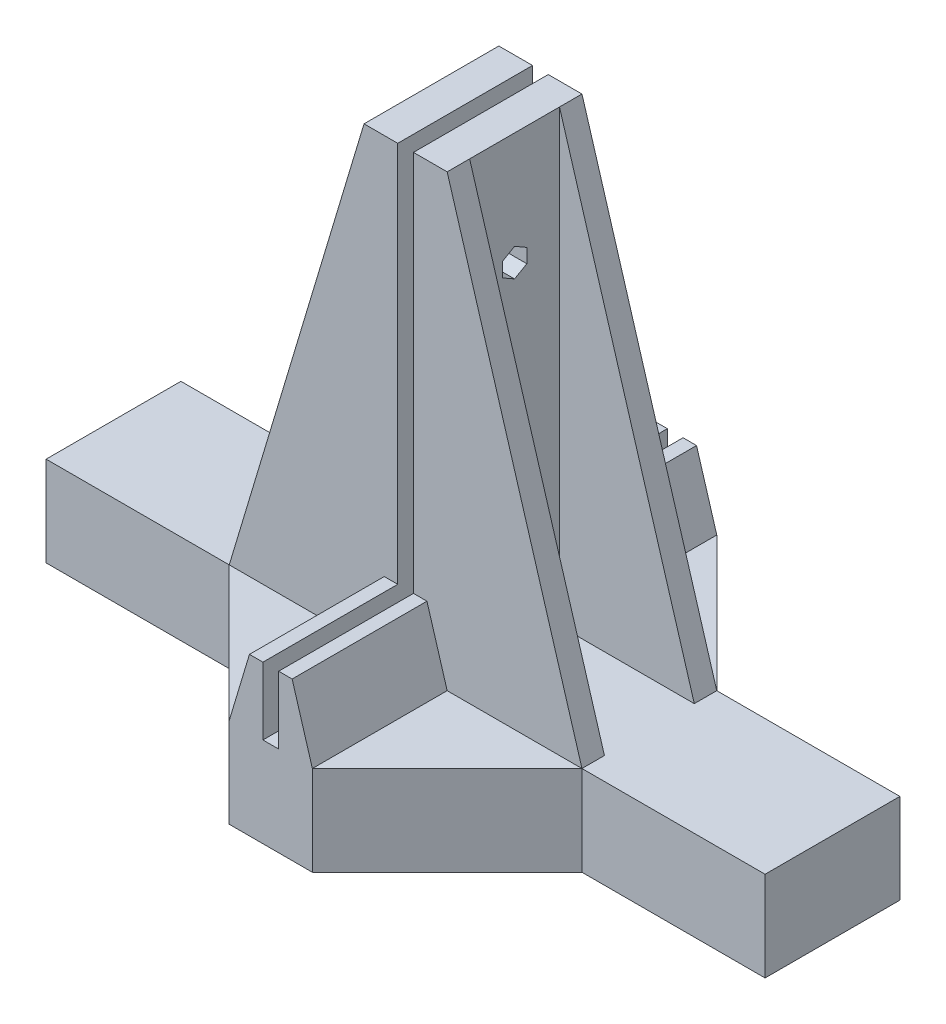
SolidWorks part; units mm, degrees
ref_plane "Front Plane" through (0, 0, 0) normal (0, 0, 1) x (1, 0, 0)
ref_plane "Top Plane" through (0, 0, 0) normal (0, 1, 0) x (1, 0, 0)
ref_plane "Right Plane" through (0, 0, 0) normal (1, 0, 0) x (0, 0, -1)
sketch "Sketch1" plane through (0, 0, 0) normal (0, 0, 1) x (1, 0, 0)
  line L0 (0, 0) -> (80, 0)
  line L1 (55, 0) -> (-55, 0) construction
  line L2 (80, 0) -> (80, 20)
  line L3 (80, 20) -> (9.25, 20)
  line L4 (9.25, 20) -> (9.25, 120)
  line L5 (9.25, 120) -> (1.75, 120)
  line L6 (1.75, 120) -> (1.75, 20)
  line L7 (1.75, 20) -> (-1.75, 20)
  line L8 (-1.75, 20) -> (-1.75, 120)
  line L9 (-1.75, 120) -> (-9.25, 120)
  line L10 (-9.25, 120) -> (-9.25, 20)
  line L11 (-9.25, 20) -> (-80, 20)
  line L12 (-80, 20) -> (-80, 0)
  line L13 (-80, 0) -> (0, 0)
  point P15 (0, 20)
  point P17 (1.6, 20)
  dimension "D1" = 80
  dimension "D2" = 20
  dimension "D4" = 100
  dimension "D5" = 7.5
  dimension "D6" = 3.5
  dimension "D7" = 160
  dimension "D8" = 7.5
extrude "Boss-Extrude3" add sketch "Sketch1" along normal blind 30
sketch "Sketch3" plane through (9.25, 0, 0) normal (1, 0, 0) x (0, 0, -1)
  line L0 (-30, 120) -> (0, 120) construction
  line L3 (-30, 20) -> (0, 20) construction
  circle A0 centre (-15, 95) radius 1.8
  circle A1 centre (-15, 45) radius 1.8
  point P0 (-15, 120)
  dimension "D3" = 3.6
  dimension "D2" = 3.6
  dimension "D4" = 25
  dimension "D1" = 50
extrude "Cut-Extrude1" cut sketch "Sketch3" against normal blind 161 and the other way blind 88
sketch "Sketch4" plane through (0, 0, 0) normal (0, 0, 1) x (1, 0, 0)
  line L0 (9.25, 120) -> (39.25, 20)
  line L1 (80, 20) -> (9.25, 20) construction
  line L2 (39.25, 20) -> (9.25, 20)
  line L3 (9.25, 20) -> (9.25, 120)
  line L4 (0, -1000) -> (0, 49000) construction
  line L6 (-9.25, 20) -> (-9.25, 120)
  line L7 (-39.25, 20) -> (-9.25, 20)
  line L8 (-9.25, 120) -> (-39.25, 20)
  dimension "D1" = 30
extrude "Boss-Extrude4" add sketch "Sketch4" along normal blind 5
extrude "Boss-Extrude5" add sketch "Sketch4<2>" against normal blind 5 from surface starting at face at (0, 50, 30)
sketch "Sketch4<2>" plane through (0, 0, 0) normal (0, 0, 1) x (1, 0, 0) same geometry as "Sketch4"
sketch "Sketch5" plane through (0, 20, 0) normal (0, 1, 0) x (1, 0, 0)
  line L0 (9.25, -25) -> (9.25, -5) construction
  line L1 (-9.25, 30) -> (9.25, 30)
  line L2 (-9.25, 30) -> (-9.25, -60) construction
  line L3 (-9.25, -60) -> (9.25, -60)
  line L4 (9.25, 30) -> (9.25, -60) construction
  line L5 (-9.25, 30) -> (9.25, -60) construction
  line L6 (-9.25, -60) -> (9.25, 30) construction
  line L7 (-9.25, -25) -> (-9.25, -5) construction
  line L8 (39.25, 0) -> (9.25, 0) construction
  line L9 (-39.25, 0) -> (-9.25, 30)
  line L10 (-39.25, 0) -> (-9.25, 0)
  line L12 (39.25, 0) -> (9.25, 30)
  line L13 (-39.25, -30) -> (-9.25, -30)
  line L14 (-39.25, -30) -> (-9.25, -60)
  line L15 (-9.25, 0) -> (-9.25, -30)
  line L16 (9.25, -60) -> (39.25, -30)
  line L17 (39.25, -30) -> (39.25, 0)
  point P0 (0, -15)
  point P5 (9.25, -15)
  dimension "D1" = 30
extrude "Boss-Extrude6" add sketch "Sketch5" against normal up to surface (20 mm away) up to face at (0, 0, 15)
sketch "Sketch7" plane through (0, 0, 30) normal (0, 0, 1) x (1, 0, 0)
  line L0 (0, -1000) -> (0, 49000) construction
  line L1 (9.25, 0) -> (-9.25, 0) construction
  line L2 (-1.75, 35) -> (-1.75, 20)
  line L3 (-1.75, 20) -> (-1.75, 120) construction
  line L4 (-1.75, 20) -> (-9.25, 20)
  line L7 (1.75, 20) -> (9.25, 20)
  line L8 (1.75, 35) -> (1.75, 20)
  line L9 (-1.75, 35) -> (-4.75, 35)
  line L10 (-4.75, 35) -> (-9.25, 20)
  line L11 (4.75, 35) -> (9.25, 20)
  line L12 (1.75, 35) -> (4.75, 35)
  point P5 (0, 0)
  dimension "D1" = 15
  dimension "D2" = 3
extrude "Boss-Extrude7" add sketch "Sketch7" along normal up to surface (30 mm away) up to face at (0, 10, 60)
extrude "Boss-Extrude8" add sketch "Sketch7<2>" along direction (0, 0, -1) on the side against the normal up to surface (60 mm away) from surface up to face at (0, 10, -30) starting at face at (59.625, 10, 0)
sketch "Sketch7<2>" plane through (0, 0, 30) normal (0, 0, 1) x (1, 0, 0) same geometry as "Sketch7"
sketch "Sketch8" plane through (9.25, 0, 0) normal (1, 0, 0) x (0, 0, -1)
  line L1 (-15, 91.8534) -> (-12.275, 93.4267)
  line L2 (-12.275, 93.4267) -> (-12.275, 96.5733)
  line L3 (-12.275, 96.5733) -> (-15, 98.1466)
  line L4 (-15, 98.1466) -> (-17.725, 96.5733)
  line L5 (-17.725, 96.5733) -> (-17.725, 93.4267)
  line L6 (-17.725, 93.4267) -> (-15, 91.8534)
  line L7 (-15, 41.8534) -> (-12.275, 43.4267)
  line L8 (-12.275, 43.4267) -> (-12.275, 46.5733)
  line L9 (-12.275, 46.5733) -> (-15, 48.1466)
  line L10 (-15, 48.1466) -> (-17.725, 46.5733)
  line L11 (-17.725, 46.5733) -> (-17.725, 43.4267)
  line L12 (-17.725, 43.4267) -> (-15, 41.8534)
  circle A0 centre (-15, 95) radius 2.725 construction
  circle A1 centre (-15, 45) radius 2.725 construction
  dimension "D1" = 5.45
extrude "Cut-Extrude2" cut sketch "Sketch8" against normal blind 4
